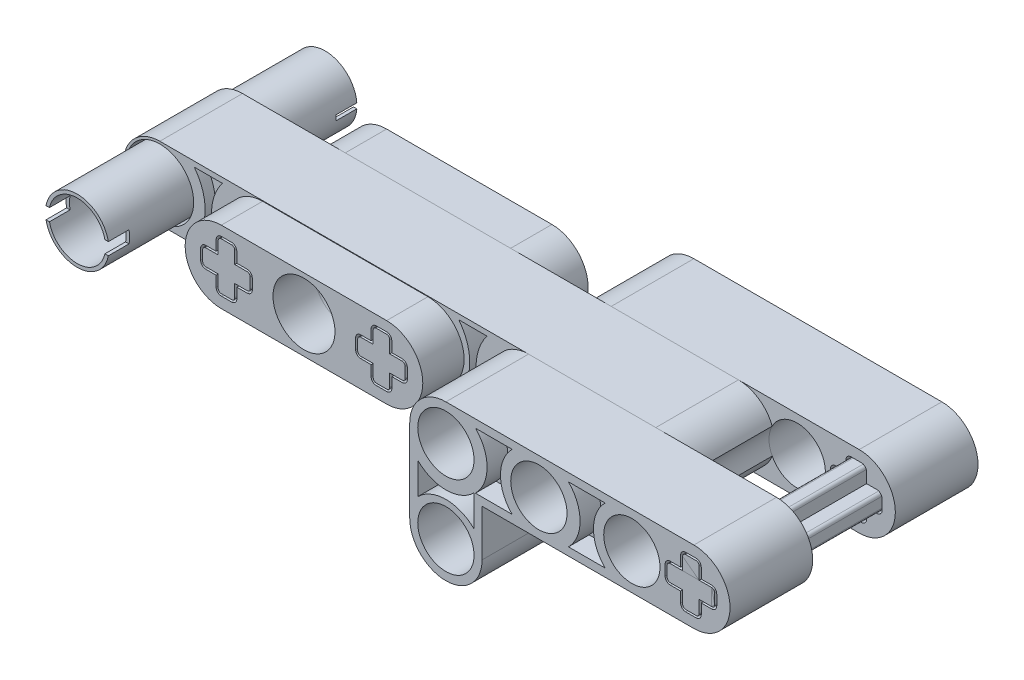
SolidWorks part; units mm, degrees
ref_plane "Front Plane" through (0, 0, 0) normal (0, 0, 1) x (1, 0, 0)
ref_plane "Top Plane" through (0, 0, 0) normal (0, 1, 0) x (1, 0, 0)
ref_plane "Right Plane" through (0, 0, 0) normal (1, 0, 0) x (0, 0, -1)
sketch "Sketch3" plane through (0, 0, 0) normal (0, 0, 1) x (1, 0, 0)
  line L0 (-24, 0) -> (24, 0) construction
  line L1 (-24, 3.5) -> (24, 3.5)
  line L2 (-24, -3.5) -> (24, -3.5)
  arc A0 (-24, 3.5) -> (-24, -3.5) centre (-24, 0) ccw
  arc A1 (24, -3.5) -> (24, 3.5) centre (24, 0) ccw
  point P3 (0, 0)
  point P8 (-27.5, 0)
  point P9 (27.5, 0)
  dimension "D1" = 7
  dimension "D2" = 55
extrude "Boss-Extrude2" add sketch "Sketch3" along normal blind 8
sketch "Sketch4" plane through (0, 0, 8) normal (0, 0, 1) x (1, 0, 0)
  line L0 (24, 3.5) -> (-24, 3.5) construction
  line L2 (-20.671, 3) -> (-17.943, 3)
  line L3 (-20.671, -3.1145) -> (-17.943, -3.1145)
  arc A1 (-20.671, 3) -> (-20.671, -3.1145) centre (-24.5637, -0.0572) cw
  arc A2 (-17.943, 3) -> (-17.943, -3.1145) centre (-14.0503, -0.0572) ccw
  point P1 (-19, -0.0572)
  point P5 (-19.614, -0.0572)
  dimension "D1" = 4.9497
  dimension "D2" = 2.728
  dimension "D3" = 19
  dimension "D4" = 0.614
  dimension "D5" = 0.5
extrude "Cut-Extrude2" cut sketch "Sketch4" against normal blind 1
sketch "Sketch5" plane through (0, 0, 8) normal (0, 0, 1) x (1, 0, 0)
  line L0 (-14.0503, -0.0572) -> (1.9497, -0.0572) construction
  line L1 (-14.0503, 3.4428) -> (1.9497, 3.4428)
  line L2 (-14.0503, -3.5572) -> (1.9497, -3.5572)
  arc A0 (-14.0503, 3.4428) -> (-14.0503, -3.5572) centre (-14.0503, -0.0572) ccw
  arc A1 (1.9497, -3.5572) -> (1.9497, 3.4428) centre (1.9497, -0.0572) ccw
  point P3 (-6.0503, -0.0572)
  dimension "D1" = 7
  dimension "D2" = 6.0503
extrude "Boss-Extrude3" add sketch "Sketch5" along normal blind 4 separate body
sketch "Sketch7" plane through (0, 0, 0) normal (0, 0, -1) x (-1, 0, 0)
  line L0 (17.943, 3) -> (20.671, 3)
  line L1 (17.943, -3.1145) -> (20.671, -3.1145)
  line L2 (-24, 3.5) -> (24, 3.5) construction
  arc A1 (17.943, 3) -> (17.943, -3.1145) centre (14.0503, -0.0572) cw
  arc A2 (20.671, 3) -> (20.671, -3.1145) centre (24.5637, -0.0572) ccw
  point P3 (19.614, -0.0572)
  point P7 (19, -0.0572)
  dimension "D1" = 4.9497
  dimension "D2" = 2.728
  dimension "D3" = 0.614
  dimension "D4" = 0.5
  dimension "D5" = 19
extrude "Cut-Extrude3" cut sketch "Sketch7" against normal blind 1
sketch "Sketch10" plane through (0, 0, 0) normal (0, 0, -1) x (-1, 0, 0)
  line L0 (-1.95, 0) -> (14.05, 0) construction
  line L1 (-1.95, 3.5) -> (14.05, 3.5)
  line L2 (-1.95, -3.5) -> (14.05, -3.5)
  line L4 (-24, 3.5) -> (24, 3.5) construction
  arc A0 (-1.95, 3.5) -> (-1.95, -3.5) centre (-1.95, 0) ccw
  arc A1 (14.05, -3.5) -> (14.05, 3.5) centre (14.05, 0) ccw
  point P2 (6.05, 0)
  point P7 (-5.45, 0)
  point P8 (17.55, 0)
  dimension "D1" = 7
  dimension "D2" = 23
  dimension "D3" = 6.05
extrude "Boss-Extrude5" add sketch "Sketch10" along normal blind 4 separate body
sketch "Sketch12" plane through (0, 0, -4) normal (0, 0, -1) x (-1, 0, 0)
  line L0 (-2.45, -1) -> (-2.45, -2)
  line L1 (-0.95, 2.5) -> (-1.95, 2.5)
  line L2 (-0.45, 2) -> (-0.45, 1)
  line L3 (-0.95, -2.5) -> (-1.95, -2.5)
  line L4 (-2.45, 2) -> (-2.45, 1)
  line L5 (-0.45, 2.5) -> (-2.45, -2.5) construction
  line L6 (-0.45, -2.5) -> (-2.45, 2.5) construction
  line L7 (0.55, 1) -> (-0.45, 1)
  line L8 (1.05, 0.5) -> (1.05, -0.5)
  line L9 (0.55, -1) -> (-0.45, -1)
  line L10 (-3.95, 0.5) -> (-3.95, -0.5)
  line L11 (1.05, 1) -> (-3.95, -1) construction
  line L12 (1.05, -1) -> (-3.95, 1) construction
  line L13 (-2.45, 1) -> (-3.45, 1)
  line L14 (-2.45, -1) -> (-3.45, -1)
  line L15 (-0.45, -1) -> (-0.45, -2)
  line L16 (-0.65, 2) -> (-0.65, 0.8)
  line L17 (0.55, 0.8) -> (-0.65, 0.8)
  line L18 (0.85, 0.5) -> (0.85, -0.5)
  line L19 (0.55, -0.8) -> (-0.65, -0.8)
  line L20 (-0.65, -0.8) -> (-0.65, -2)
  line L21 (-0.95, -2.3) -> (-1.95, -2.3)
  line L22 (-2.25, -0.8) -> (-2.25, -2)
  line L23 (-2.25, -0.8) -> (-3.45, -0.8)
  line L24 (-3.75, 0.5) -> (-3.75, -0.5)
  line L25 (-2.25, 0.8) -> (-3.45, 0.8)
  line L26 (-2.25, 2) -> (-2.25, 0.8)
  line L27 (-0.95, 2.3) -> (-1.95, 2.3)
  line L28 (12.5509, -1.0052) -> (12.5509, -2.0052)
  line L29 (14.05, 2.5) -> (13.05, 2.5)
  line L30 (14.55, 1.9943) -> (14.55, 0.9943)
  line L31 (14.051, -2.5051) -> (13.051, -2.5051)
  line L32 (12.5491, 1.9947) -> (12.5491, 0.9947)
  line L33 (15.55, 0.9943) -> (14.55, 0.9943)
  line L34 (16.05, 0.4943) -> (16.05, -0.5057)
  line L35 (15.5509, -1.0051) -> (14.5509, -1.0051)
  line L36 (11.05, 0.4943) -> (11.05, -0.5057)
  line L37 (12.5491, 0.9947) -> (11.5491, 0.9947)
  line L38 (12.5509, -1.0052) -> (11.5509, -1.0052)
  line L39 (14.5509, -1.0051) -> (14.5509, -2.0051)
  line L40 (14.35, 1.9943) -> (14.35, 0.7943)
  line L41 (15.55, 0.7943) -> (14.35, 0.7943)
  line L42 (15.85, 0.4943) -> (15.85, -0.5057)
  line L43 (15.55, -0.8057) -> (14.35, -0.8057)
  line L44 (14.35, -0.8057) -> (14.35, -2.0057)
  line L45 (14.05, -2.3057) -> (13.05, -2.3057)
  line L46 (12.75, -0.8057) -> (12.75, -2.0057)
  line L47 (12.75, -0.8057) -> (11.55, -0.8057)
  line L48 (11.25, 0.4943) -> (11.25, -0.5057)
  line L49 (12.75, 0.7943) -> (11.55, 0.7943)
  line L50 (12.75, 1.9943) -> (12.75, 0.7943)
  line L51 (14.05, 2.2943) -> (13.05, 2.2943)
  line L52 (14.55, 2.5) -> (12.55, -2.5) construction
  line L53 (14.55, -2.5) -> (12.55, 2.5) construction
  line L54 (16.05, 1) -> (11.05, -1) construction
  line L55 (16.05, -1) -> (11.05, 1) construction
  line L56 (14.05, 3.5) -> (-1.95, 3.5) construction
  arc A0 (-1.95, -2.5) -> (-2.45, -2) centre (-1.95, -2) cw
  arc A1 (-0.45, -2) -> (-0.95, -2.5) centre (-0.95, -2) cw
  arc A2 (-0.95, 2.5) -> (-0.45, 2) centre (-0.95, 2) cw
  arc A3 (-1.95, 2.5) -> (-2.45, 2) centre (-1.95, 2) ccw
  arc A4 (0.55, 1) -> (1.05, 0.5) centre (0.55, 0.5) cw
  arc A5 (1.05, -0.5) -> (0.55, -1) centre (0.55, -0.5) cw
  arc A6 (-3.45, -1) -> (-3.95, -0.5) centre (-3.45, -0.5) cw
  arc A7 (-3.45, 1) -> (-3.95, 0.5) centre (-3.45, 0.5) ccw
  arc A8 (0.55, 0.8) -> (0.85, 0.5) centre (0.55, 0.5) cw
  arc A9 (0.85, -0.5) -> (0.55, -0.8) centre (0.55, -0.5) cw
  arc A10 (-0.65, -2) -> (-0.95, -2.3) centre (-0.95, -2) cw
  arc A11 (-1.95, -2.3) -> (-2.25, -2) centre (-1.95, -2) cw
  arc A12 (-3.45, -0.8) -> (-3.75, -0.5) centre (-3.45, -0.5) cw
  arc A13 (-3.45, 0.8) -> (-3.75, 0.5) centre (-3.45, 0.5) ccw
  arc A14 (-1.95, 2.3) -> (-2.25, 2) centre (-1.95, 2) ccw
  arc A15 (-0.95, 2.3) -> (-0.65, 2) centre (-0.95, 2) cw
  arc A16 (13.051, -2.5051) -> (12.5509, -2.0052) centre (13.0509, -2.0051) cw
  arc A17 (14.5509, -2.0051) -> (14.051, -2.5051) centre (14.0509, -2.0051) cw
  arc A18 (14.05, 2.5) -> (14.55, 1.9943) centre (14.05, 2) cw
  arc A19 (13.05, 2.5) -> (12.5491, 1.9947) centre (13.0491, 2) ccw
  arc A20 (15.55, 0.9943) -> (16.05, 0.4943) centre (15.55, 0.4943) cw
  arc A21 (16.05, -0.5057) -> (15.5509, -1.0051) centre (15.55, -0.5051) cw
  arc A22 (11.5509, -1.0052) -> (11.05, -0.5057) centre (11.55, -0.5053) cw
  arc A23 (11.5491, 0.9947) -> (11.05, 0.4943) centre (11.55, 0.4948) ccw
  arc A24 (15.55, 0.7943) -> (15.85, 0.4943) centre (15.55, 0.4943) cw
  arc A25 (15.85, -0.5057) -> (15.55, -0.8057) centre (15.55, -0.5057) cw
  arc A26 (14.35, -2.0057) -> (14.05, -2.3057) centre (14.05, -2.0057) cw
  arc A27 (13.05, -2.3057) -> (12.75, -2.0057) centre (13.05, -2.0057) cw
  arc A28 (11.55, -0.8057) -> (11.25, -0.5057) centre (11.55, -0.5057) cw
  arc A29 (11.55, 0.7943) -> (11.25, 0.4943) centre (11.55, 0.4943) ccw
  arc A30 (13.05, 2.2943) -> (12.75, 1.9943) centre (13.05, 1.9943) ccw
  arc A31 (14.05, 2.2943) -> (14.35, 1.9943) centre (14.05, 1.9943) cw
  arc A33 (14.05, -3.5) -> (14.05, 3.5) centre (14.05, 0) ccw construction
  point P0 (0, 0)
  point P6 (0, 0)
  point P69 (13.55, 0)
  point P74 (13.55, 0)
  point P135 (11.05, -0.0057)
  point P140 (17.55, 0)
  point P141 (-1.45, 0)
  dimension "D5" = 0.5
  dimension "D3" = 0.5
  dimension "D2" = 1
  dimension "D4" = 5
  dimension "D6" = 1
  dimension "D9" = 6.5
  dimension "D10" = 4
  dimension "D8" = 1
  dimension "D11" = 5
  dimension "D12" = 0.2
  dimension "D13" = 0.2
  dimension "D14" = 15
  dimension "D15" = 1
  dimension "D16" = 0.2009
  dimension "D17" = 0.2
  dimension "D18" = 0.2009
  dimension "D19" = 0.1994
  dimension "D20" = 0.1991
  dimension "D7" = 0.2
extrude "Cut-Extrude6" cut sketch "Sketch12" against normal through all
sketch "Sketch13" plane through (0, 0, 8) normal (0, 0, 1) x (1, 0, 0)
  circle A0 centre (-24, 0) radius 3.275
  circle A1 centre (-24, 0) radius 3.075
  dimension "D1" = 6.55
  dimension "D2" = 6.15
extrude "Cut-Extrude8" cut sketch "Sketch13" against normal through all
sketch "Sketch17" plane through (0, 0, -4) normal (0, 0, -1) x (-1, 0, 0)
  line L0 (-2.4539, -1) -> (-2.4539, -2)
  line L1 (-0.9539, 2.5) -> (-1.9539, 2.5)
  line L2 (-0.4539, 2) -> (-0.4539, 1)
  line L3 (-0.9539, -2.5) -> (-1.9539, -2.5)
  line L4 (-2.4539, 2) -> (-2.4539, 1)
  line L5 (-0.4539, 2.5) -> (-2.4539, -2.5) construction
  line L6 (-0.4539, -2.5) -> (-2.4539, 2.5) construction
  line L7 (0.5461, 1) -> (-0.4539, 1)
  line L8 (1.0461, 0.5) -> (1.0461, -0.5)
  line L9 (0.5461, -1) -> (-0.4539, -1)
  line L10 (-3.9539, 0.5) -> (-3.9539, -0.5)
  line L11 (1.0461, 1) -> (-3.9539, -1) construction
  line L12 (1.0461, -1) -> (-3.9539, 1) construction
  line L13 (-2.4539, 1) -> (-3.4539, 1)
  line L14 (-2.4539, -1) -> (-3.4539, -1)
  line L15 (-0.4539, -1) -> (-0.4539, -2)
  line L16 (-0.6539, 2) -> (-0.6539, 0.8)
  line L17 (0.5461, 0.8) -> (-0.6539, 0.8)
  line L18 (0.8461, 0.5) -> (0.8461, -0.5)
  line L19 (0.5461, -0.8) -> (-0.6539, -0.8)
  line L20 (-0.6539, -0.8) -> (-0.6539, -2)
  line L21 (-0.9539, -2.3) -> (-1.9539, -2.3)
  line L22 (-2.2539, -0.8) -> (-2.2539, -2)
  line L23 (-2.2539, -0.8) -> (-3.4539, -0.8)
  line L24 (-3.7539, 0.5) -> (-3.7539, -0.5)
  line L25 (-2.2539, 0.8) -> (-3.4539, 0.8)
  line L26 (-2.2539, 2) -> (-2.2539, 0.8)
  line L27 (-0.9539, 2.3) -> (-1.9539, 2.3)
  line L52 (12.55, -1) -> (12.55, -2)
  line L53 (14.05, 2.5) -> (13.05, 2.5)
  line L54 (14.55, 2) -> (14.55, 1)
  line L55 (14.05, -2.5) -> (13.05, -2.5)
  line L56 (14.05, 3.5) -> (-1.95, 3.5) construction
  line L57 (12.55, 2) -> (12.55, 1)
  line L58 (15.55, 1) -> (14.55, 1)
  line L59 (16.05, 0.5) -> (16.05, -0.5)
  line L60 (15.55, -1) -> (14.55, -1)
  line L61 (11.05, 0.5) -> (11.05, -0.5)
  line L62 (12.55, 1) -> (11.55, 1)
  line L63 (12.55, -1) -> (11.55, -1)
  line L64 (14.55, -1) -> (14.55, -2)
  line L65 (14.35, 2) -> (14.35, 0.8)
  line L66 (15.55, 0.8) -> (14.35, 0.8)
  line L67 (15.85, 0.5) -> (15.85, -0.5)
  line L68 (15.55, -0.8) -> (14.35, -0.8)
  line L69 (14.35, -0.8) -> (14.35, -2)
  line L70 (14.05, -2.3) -> (13.05, -2.3)
  line L71 (12.75, -0.8) -> (12.75, -2)
  line L72 (12.75, -0.8) -> (11.55, -0.8)
  line L73 (11.25, 0.5) -> (11.25, -0.5)
  line L74 (12.75, 0.8) -> (11.55, 0.8)
  line L75 (12.75, 2) -> (12.75, 0.8)
  line L76 (14.05, 2.3) -> (13.05, 2.3)
  line L77 (14.55, 2.5) -> (12.55, -2.5) construction
  line L78 (14.55, -2.5) -> (12.55, 2.5) construction
  line L79 (16.05, 1) -> (11.05, -1) construction
  line L80 (16.05, -1) -> (11.05, 1) construction
  arc A0 (-1.9539, -2.5) -> (-2.4539, -2) centre (-1.9539, -2) cw
  arc A1 (-0.4539, -2) -> (-0.9539, -2.5) centre (-0.9539, -2) cw
  arc A2 (-0.9539, 2.5) -> (-0.4539, 2) centre (-0.9539, 2) cw
  arc A3 (-1.9539, 2.5) -> (-2.4539, 2) centre (-1.9539, 2) ccw
  arc A4 (0.5461, 1) -> (1.0461, 0.5) centre (0.5461, 0.5) cw
  arc A5 (1.0461, -0.5) -> (0.5461, -1) centre (0.5461, -0.5) cw
  arc A6 (-3.4539, -1) -> (-3.9539, -0.5) centre (-3.4539, -0.5) cw
  arc A7 (-3.4539, 1) -> (-3.9539, 0.5) centre (-3.4539, 0.5) ccw
  arc A8 (0.5461, 0.8) -> (0.8461, 0.5) centre (0.5461, 0.5) cw
  arc A9 (0.8461, -0.5) -> (0.5461, -0.8) centre (0.5461, -0.5) cw
  arc A10 (-0.6539, -2) -> (-0.9539, -2.3) centre (-0.9539, -2) cw
  arc A11 (-1.9539, -2.3) -> (-2.2539, -2) centre (-1.9539, -2) cw
  arc A12 (-3.4539, -0.8) -> (-3.7539, -0.5) centre (-3.4539, -0.5) cw
  arc A13 (-3.4539, 0.8) -> (-3.7539, 0.5) centre (-3.4539, 0.5) ccw
  arc A14 (-1.9539, 2.3) -> (-2.2539, 2) centre (-1.9539, 2) ccw
  arc A15 (-0.9539, 2.3) -> (-0.6539, 2) centre (-0.9539, 2) cw
  arc A32 (13.05, -2.5) -> (12.55, -2) centre (13.05, -2) cw
  arc A33 (14.55, -2) -> (14.05, -2.5) centre (14.05, -2) cw
  arc A34 (14.05, 2.5) -> (14.55, 2) centre (14.05, 2) cw
  arc A35 (13.05, 2.5) -> (12.55, 2) centre (13.05, 2) ccw
  arc A36 (15.55, 1) -> (16.05, 0.5) centre (15.55, 0.5) cw
  arc A37 (16.05, -0.5) -> (15.55, -1) centre (15.55, -0.5) cw
  arc A38 (11.55, -1) -> (11.05, -0.5) centre (11.55, -0.5) cw
  arc A39 (11.55, 1) -> (11.05, 0.5) centre (11.55, 0.5) ccw
  arc A40 (15.55, 0.8) -> (15.85, 0.5) centre (15.55, 0.5) cw
  arc A41 (15.85, -0.5) -> (15.55, -0.8) centre (15.55, -0.5) cw
  arc A42 (14.35, -2) -> (14.05, -2.3) centre (14.05, -2) cw
  arc A43 (13.05, -2.3) -> (12.75, -2) centre (13.05, -2) cw
  arc A44 (11.55, -0.8) -> (11.25, -0.5) centre (11.55, -0.5) cw
  arc A45 (11.55, 0.8) -> (11.25, 0.5) centre (11.55, 0.5) ccw
  arc A46 (13.05, 2.3) -> (12.75, 2) centre (13.05, 2) ccw
  arc A47 (14.05, 2.3) -> (14.35, 2) centre (14.05, 2) cw
  arc A48 (14.05, -3.5) -> (14.05, 3.5) centre (14.05, 0) ccw construction
  arc A49 (-1.95, 3.5) -> (-1.95, -3.5) centre (-1.95, 0) ccw construction
  point P0 (-0.0039, 0.2841)
  point P5 (-0.0039, 0.2841)
  point P67 (15, 0.2841)
  point P72 (15, 0.2841)
  point P137 (17.55, 0)
  point P141 (-5.45, 0)
  dimension "D3" = 0.5
  dimension "D4" = 2
  dimension "D1" = 5
  dimension "D2" = 1
  dimension "D5" = 6.5
  dimension "D6" = 6.4961
  dimension "D15" = 1
  dimension "D16" = 1.2
extrude "Cut-Extrude9" cut sketch "Sketch17" against normal through all
sketch "Sketch20" plane through (0, 0, -4) normal (0, 0, -1) x (-1, 0, 0)
  line L0 (14.05, 3.5) -> (-1.95, 3.5) construction
  circle A0 centre (6.05, 0) radius 3
  arc A1 (-1.95, 3.5) -> (-1.95, -3.5) centre (-1.95, 0) ccw construction
  dimension "D1" = 6
  dimension "D2" = 3.5
  dimension "D3" = 8
extrude "Cut-Extrude10" cut sketch "Sketch20" against normal through all
sketch "Sketch21" plane through (0, 0, 8) normal (0, 0, 1) x (1, 0, 0)
  circle A0 centre (-24, 0) radius 3.075
  circle A1 centre (-24, 0) radius 2.75
extrude "Boss-Extrude6" add sketch "Sketch21" along normal blind 8 and the other way blind 16
sketch "Sketch22" plane through (0, 0, 16) normal (0, 0, 1) x (1, 0, 0)
  line L1 (-20.779, 0.5924) -> (-27.221, 0.5924)
  line L2 (-20.779, 0.5924) -> (-20.779, -0.5924)
  line L3 (-20.779, -0.5924) -> (-27.221, -0.5924)
  line L4 (-27.221, 0.5924) -> (-27.221, -0.5924)
  line L5 (-20.779, 0.5924) -> (-27.221, -0.5924) construction
  line L6 (-20.779, -0.5924) -> (-27.221, 0.5924) construction
  circle A0 centre (-24, 0) radius 3.275 construction
  point P0 (-24, 0)
  dimension "D1" = 1.1848
extrude "Cut-Extrude11" cut sketch "Sketch22" against normal blind 2
sketch "Sketch23" plane through (0, 0, -8) normal (0, 0, -1) x (-1, 0, 0)
  line L1 (27.2654, 0.25) -> (20.7346, 0.25)
  line L2 (27.2654, 0.25) -> (27.2654, -0.25)
  line L3 (27.2654, -0.25) -> (20.7346, -0.25)
  line L4 (20.7346, 0.25) -> (20.7346, -0.25)
  line L5 (27.2654, 0.25) -> (20.7346, -0.25) construction
  line L6 (27.2654, -0.25) -> (20.7346, 0.25) construction
  circle A0 centre (24, 0) radius 3.275 construction
  point P0 (24, 0)
  dimension "D1" = 0.5
extrude "Cut-Extrude12" cut sketch "Sketch23" against normal blind 2
sketch "Sketch24" plane through (0, 0, 8) normal (0, 0, 1) x (1, 0, 0)
  circle A0 centre (-24, 0) radius 2.75
extrude "Cut-Extrude13" cut sketch "Sketch24" against normal through all
sketch "Sketch26" plane through (0, 0, 8) normal (0, 0, 1) x (1, 0, 0)
  line L0 (4.943, 3) -> (7.671, 3)
  line L1 (4.943, -3.1145) -> (7.671, -3.1145)
  line L2 (24, 3.5) -> (-24, 3.5) construction
  arc A0 (4.943, 3) -> (4.943, -3.1145) centre (1.0503, -0.0572) cw
  arc A1 (7.671, 3) -> (7.671, -3.1145) centre (11.5637, -0.0572) ccw
  point P0 (6.614, -0.0572)
  point P4 (6, -0.0572)
  dimension "D1" = 4.9497
  dimension "D5" = 6
  dimension "D2" = 2.728
  dimension "D3" = 0.614
  dimension "D4" = 0.5
extrude "Cut-Extrude14" cut sketch "Sketch26" against normal blind 2
ref_plane "Plane1" through (0, 0, 8) normal (0, 0, 1) x (1, 0, 0)
sketch "Sketch29" plane through (0, 0, 8) normal (0, 0, 1) x (1, 0, 0)
  line L0 (8.187, 0) -> (8.187, -8)
  line L1 (11.687, 3.5) -> (35.687, 3.5)
  line L2 (35.687, -3.5) -> (15.187, -3.5)
  line L3 (15.187, -3.5) -> (15.187, -8)
  line L4 (24, 3.5) -> (-24, 3.5) construction
  arc A0 (8.187, -8) -> (15.187, -8) centre (11.687, -8) ccw
  arc A1 (8.187, 0) -> (11.687, 3.5) centre (11.687, 0) cw
  arc A2 (15.187, -8) -> (8.187, -8) centre (11.687, -8) cw
  arc A3 (35.687, 3.5) -> (35.687, -3.5) centre (35.687, 0) cw
  point P0 (39.187, 0)
  point P10 (11.687, -11.5)
  dimension "D5" = 3.5
  dimension "D6" = 3.5
  dimension "D7" = 3.5
  dimension "D10" = 11.687
  dimension "D1" = 31
  dimension "D2" = 15
  dimension "D3" = 7
  dimension "D4" = 7
  dimension "D8" = 8.187
  dimension "D9" = 11.687
extrude "Boss-Extrude8" add sketch "Sketch29" along normal blind 8 separate body contours A3 L1 A1 L0 A0 L3 L2 region at (21.1948, -1.4269, 8)
sketch "Sketch36" plane through (0, 0, 0) normal (0, 0, -1) x (-1, 0, 0)
  line L0 (-35.687, -3.5) -> (-15.187, -3.5) construction
  line L1 (-24, 3.5) -> (24, 3.5) construction
  line L2 (-8.187, 0) -> (-8.187, -8) construction
  line L3 (-35.687, 3.5) -> (-11.687, 3.5)
  line L4 (-8.187, 0) -> (-8.187, -8)
  line L5 (-15.187, -8) -> (-15.187, -3.5)
  line L6 (-15.187, -3.5) -> (-35.687, -3.5)
  arc A1 (-15.187, -8) -> (-8.187, -8) centre (-11.687, -8) ccw
  arc A3 (-15.187, -8) -> (-8.187, -8) centre (-11.687, -8) ccw construction
  arc A4 (-35.687, 3.5) -> (-35.687, -3.5) centre (-35.687, 0) ccw
  arc A5 (-35.687, 3.5) -> (-35.687, -3.5) centre (-35.687, 0) ccw construction
  arc A6 (-11.687, 3.5) -> (-8.187, 0) centre (-11.687, 0) cw
extrude "Boss-Extrude10" add sketch "Sketch36" along normal blind 8 separate body
sketch "Sketch40" plane through (0, 0, -8) normal (0, 0, -1) x (-1, 0, 0)
  line L0 (-36.4025, -1) -> (-36.4025, -2)
  line L1 (-34.9025, 2.5) -> (-35.9025, 2.5)
  line L2 (-34.4025, 2) -> (-34.4025, 1)
  line L3 (-34.9025, -2.5) -> (-35.9025, -2.5)
  line L4 (-36.4025, 2) -> (-36.4025, 1)
  line L5 (-34.4025, 2.5) -> (-36.4025, -2.5) construction
  line L6 (-34.4025, -2.5) -> (-36.4025, 2.5) construction
  line L7 (-33.4025, 1) -> (-34.4025, 1)
  line L8 (-32.9025, 0.5) -> (-32.9025, -0.5)
  line L9 (-33.4025, -1) -> (-34.4025, -1)
  line L10 (-37.9025, 0.5) -> (-37.9025, -0.5)
  line L11 (-32.9025, 1) -> (-37.9025, -1) construction
  line L12 (-32.9025, -1) -> (-37.9025, 1) construction
  line L13 (-36.4025, 1) -> (-37.4025, 1)
  line L14 (-36.4025, -1) -> (-37.4025, -1)
  line L15 (-34.4025, -1) -> (-34.4025, -2)
  line L16 (-34.6025, 2) -> (-34.6025, 0.8)
  line L17 (-33.4025, 0.8) -> (-34.6025, 0.8)
  line L18 (-33.1025, 0.5) -> (-33.1025, -0.5)
  line L19 (-33.4025, -0.8) -> (-34.6025, -0.8)
  line L20 (-34.6025, -0.8) -> (-34.6025, -2)
  line L21 (-34.9025, -2.3) -> (-35.9025, -2.3)
  line L22 (-36.2025, -0.8) -> (-36.2025, -2)
  line L23 (-36.2025, -0.8) -> (-37.4025, -0.8)
  line L24 (-37.7025, 0.5) -> (-37.7025, -0.5)
  line L25 (-36.2025, 0.8) -> (-37.4025, 0.8)
  line L26 (-36.2025, 2) -> (-36.2025, 0.8)
  line L27 (-34.9025, 2.3) -> (-35.9025, 2.3)
  line L28 (-11.687, 3.5) -> (-35.687, 3.5) construction
  arc A0 (-35.9025, -2.5) -> (-36.4025, -2) centre (-35.9025, -2) cw
  arc A1 (-34.4025, -2) -> (-34.9025, -2.5) centre (-34.9025, -2) cw
  arc A2 (-34.9025, 2.5) -> (-34.4025, 2) centre (-34.9025, 2) cw
  arc A3 (-35.9025, 2.5) -> (-36.4025, 2) centre (-35.9025, 2) ccw
  arc A4 (-33.4025, 1) -> (-32.9025, 0.5) centre (-33.4025, 0.5) cw
  arc A5 (-32.9025, -0.5) -> (-33.4025, -1) centre (-33.4025, -0.5) cw
  arc A6 (-37.4025, -1) -> (-37.9025, -0.5) centre (-37.4025, -0.5) cw
  arc A7 (-37.4025, 1) -> (-37.9025, 0.5) centre (-37.4025, 0.5) ccw
  arc A8 (-33.4025, 0.8) -> (-33.1025, 0.5) centre (-33.4025, 0.5) cw
  arc A9 (-33.1025, -0.5) -> (-33.4025, -0.8) centre (-33.4025, -0.5) cw
  arc A10 (-34.6025, -2) -> (-34.9025, -2.3) centre (-34.9025, -2) cw
  arc A11 (-35.9025, -2.3) -> (-36.2025, -2) centre (-35.9025, -2) cw
  arc A12 (-37.4025, -0.8) -> (-37.7025, -0.5) centre (-37.4025, -0.5) cw
  arc A13 (-37.4025, 0.8) -> (-37.7025, 0.5) centre (-37.4025, 0.5) ccw
  arc A14 (-35.9025, 2.3) -> (-36.2025, 2) centre (-35.9025, 2) ccw
  arc A15 (-34.9025, 2.3) -> (-34.6025, 2) centre (-34.9025, 2) cw
  arc A16 (-35.687, 3.5) -> (-35.687, -3.5) centre (-35.687, 0) ccw construction
  point P0 (-33.9525, 0.3228)
  point P5 (-33.9525, 0.3228)
  point P68 (-35.4025, 2.3)
  point P72 (-39.187, 0)
  dimension "D3" = 0.5
  dimension "D1" = 5
  dimension "D2" = 1
  dimension "D4" = 1
  dimension "D5" = 0.2
  dimension "D6" = 0.2
  dimension "D7" = 1.2845
extrude "Cut-Extrude19" cut sketch "Sketch40" against normal through all
sketch "Sketch41" plane through (0, 0, -8) normal (0, 0, -1) x (-1, 0, 0)
  line L40 (-34.6025, 2) -> (-34.6025, 0.8)
  line L41 (-33.4025, 0.8) -> (-34.6025, 0.8)
  line L42 (-33.1025, 0.5) -> (-33.1025, -0.5)
  line L43 (-33.4025, -0.8) -> (-34.6025, -0.8)
  line L44 (-34.6025, -0.8) -> (-34.6025, -2)
  line L45 (-34.9025, -2.3) -> (-35.9025, -2.3)
  line L46 (-36.2025, -0.8) -> (-36.2025, -2)
  line L47 (-36.2025, -0.8) -> (-37.4025, -0.8)
  line L48 (-37.7025, 0.5) -> (-37.7025, -0.5)
  line L49 (-36.2025, 0.8) -> (-37.4025, 0.8)
  line L50 (-36.2025, 2) -> (-36.2025, 0.8)
  line L51 (-34.9025, 2.3) -> (-35.9025, 2.3)
  arc A24 (-33.4025, 0.8) -> (-33.1025, 0.5) centre (-33.4025, 0.5) cw
  arc A25 (-33.1025, -0.5) -> (-33.4025, -0.8) centre (-33.4025, -0.5) cw
  arc A26 (-34.6025, -2) -> (-34.9025, -2.3) centre (-34.9025, -2) cw
  arc A27 (-35.9025, -2.3) -> (-36.2025, -2) centre (-35.9025, -2) cw
  arc A28 (-37.4025, -0.8) -> (-37.7025, -0.5) centre (-37.4025, -0.5) cw
  arc A29 (-37.4025, 0.8) -> (-37.7025, 0.5) centre (-37.4025, 0.5) ccw
  arc A30 (-35.9025, 2.3) -> (-36.2025, 2) centre (-35.9025, 2) ccw
  arc A31 (-34.9025, 2.3) -> (-34.6025, 2) centre (-34.9025, 2) cw
  point P0 (-33.8342, 0.1396)
  point P5 (-33.8342, 0.1396)
extrude "Boss-Extrude11" add sketch "Sketch41" against normal blind 24 separate body
sketch "Sketch42" plane through (0, 0, -8) normal (0, 0, -1) x (-1, 0, 0)
  circle A0 centre (-11.687, 0) radius 2.7252
  circle A1 centre (-20.687, 0) radius 2.7252
  circle A2 centre (-29.687, 0) radius 2.7252
  circle A3 centre (-20.687, -8) radius 2.7252 [skipped]
  circle A4 centre (-29.687, -8) radius 2.7252 [skipped]
  circle A5 centre (-11.687, -8) radius 2.7252
  dimension "D3" = 5.4504
  dimension "D4" = 9
  dimension "D5" = 8
  dimension "D6" = 3.5
  dimension "D1" = 3
  dimension "D2" = 2
extrude "Cut-Extrude20" cut sketch "Sketch42" against normal through all
sketch "Sketch43" plane through (0, 0, -8) normal (0, 0, -1) x (-1, 0, 0)
  line L0 (-26.9618, 2.7252) -> (-23.4122, 2.7252)
  line L2 (-23.4122, -2.7252) -> (-26.9618, -2.7252)
  line L4 (-11.687, 3.5) -> (-35.687, 3.5) construction
  line L5 (-17.9618, 2.7252) -> (-14.4122, 2.7252)
  line L6 (-14.4122, -2.7252) -> (-17.9618, -2.7252)
  arc A0 (-26.9618, 2.7252) -> (-26.9618, -2.7252) centre (-29.687, 0) cw
  arc A1 (-23.4122, 2.7252) -> (-23.4122, -2.7252) centre (-20.687, 0) ccw
  arc A2 (-34.9025, -2.3) -> (-34.6025, -2) centre (-34.9025, -2) ccw construction
  arc A3 (-14.4122, 2.7252) -> (-14.4122, -2.7252) centre (-11.687, 0) ccw
  arc A4 (-17.9618, 2.7252) -> (-17.9618, -2.7252) centre (-20.687, 0) cw
  dimension "D3" = 3.854
  dimension "D4" = 7.9407
  dimension "D1" = 3.5496
  dimension "D2" = 0.7748
  dimension "D5" = 4.9155
  dimension "D7" = 5.4504
  dimension "D6" = 2
extrude "Cut-Extrude21" cut sketch "Sketch43" against normal blind 2
sketch "Sketch44" plane through (0, 0, 16) normal (0, 0, 1) x (1, 0, 0)
  line L0 (14.5469, 2.7252) -> (18.0965, 2.7252)
  line L1 (18.0965, -2.7252) -> (14.5469, -2.7252)
  line L2 (23.5469, 2.7252) -> (27.0965, 2.7252)
  line L3 (27.0965, -2.7252) -> (23.5469, -2.7252)
  line L4 (35.687, -3.5) -> (15.187, -3.5) construction
  line L5 (11.687, 3.5) -> (35.687, 3.5) construction
  arc A0 (14.5469, 2.7252) -> (14.5469, -2.7252) centre (11.8217, 0) cw
  arc A1 (18.0965, 2.7252) -> (18.0965, -2.7252) centre (20.8217, 0) ccw
  arc A2 (27.0965, 2.7252) -> (27.0965, -2.7252) centre (29.8217, 0) ccw
  arc A3 (23.5469, 2.7252) -> (23.5469, -2.7252) centre (20.8217, 0) cw
  circle A4 centre (11.687, 0) radius 2.7252 construction
  point P12 (11.687, 2.7252)
  dimension "D2" = 3.854
  dimension "D8" = 3.854
  dimension "D1" = 3.5496
  dimension "D3" = 5.4504
  dimension "D4" = 12.5969
  dimension "D5" = 0.7748
  dimension "D6" = 5.4504
  dimension "D7" = 5.4504
  dimension "D9" = 0.7748
  dimension "D10" = 3.5496
extrude "Cut-Extrude22" cut sketch "Sketch44" against normal blind 2
sketch "Sketch45" plane through (0, 0, 16) normal (0, 0, 1) x (1, 0, 0)
  line L0 (8.971, -2.7586) -> (8.971, -5.8018)
  line L2 (14.418, -5.8018) -> (14.418, -2.7586)
  line L4 (8.187, 0) -> (8.187, -8) construction
  arc A0 (8.971, -2.7586) -> (14.418, -2.7586) centre (11.6945, -0.0317) ccw
  arc A1 (8.971, -5.8018) -> (14.418, -5.8018) centre (11.6945, -8.5287) cw
  dimension "D2" = 3.854
  dimension "D1" = 0.784
  dimension "D3" = 2.1982
  dimension "D4" = 5.447
  dimension "D5" = 3.0433
extrude "Cut-Extrude23" cut sketch "Sketch45" against normal blind 2
sketch "Sketch46" plane through (0, 0, -8) normal (0, 0, -1) x (-1, 0, 0)
  line L0 (-14.4122, -2.8151) -> (-14.4122, -5.8583)
  line L1 (-8.9652, -5.8583) -> (-8.9652, -2.8151)
  line L2 (-15.187, -3.5) -> (-15.187, -8) construction
  arc A0 (-14.4122, -2.8151) -> (-8.9652, -2.8151) centre (-11.6887, -0.0882) ccw
  arc A1 (-14.4122, -5.8583) -> (-8.9652, -5.8583) centre (-11.6887, -8.5852) cw
  circle A2 centre (-11.687, -8) radius 2.7252 construction
  point P7 (-14.4122, -8)
  dimension "D1" = 3.854
  dimension "D2" = 5.447
  dimension "D3" = 3.0433
  dimension "D4" = 0.7748
  dimension "D5" = 3.4634
extrude "Cut-Extrude24" cut sketch "Sketch46" against normal blind 2
sketch "Sketch48" plane through (0, 0, 0) normal (0, 0, -1) x (-1, 0, 0)
  line L0 (-7.9381, 3.001) -> (-5.2101, 3.001)
  line L1 (-7.9381, -3.1134) -> (-5.2101, -3.1134)
  line L2 (24, -3.5) -> (-24, -3.5) construction
  arc A0 (-7.9381, 3.001) -> (-7.9381, -3.1134) centre (-11.8309, -0.0562) cw
  arc A1 (-5.2101, 3.001) -> (-5.2101, -3.1134) centre (-1.3174, -0.0562) ccw
  point P0 (-6.2671, -0.0562)
  point P4 (-6.8811, -0.0562)
  dimension "D1" = 4.9497
  dimension "D2" = 2.728
  dimension "D3" = 0.614
  dimension "D4" = 0.3866
  dimension "D5" = 5.2101
extrude "Cut-Extrude25" cut sketch "Sketch48" against normal blind 2
ref_plane "Plane2" through (0, 0, -8) normal (0, 0, -1) x (-1, 0, 0)
sketch "Sketch49" plane through (0, 0, -8) normal (0, 0, -1) x (-1, 0, 0)
  line L0 (-28.2478, -3.5) -> (-16.833, -3.5) construction
  line L4 (-11.687, 3.5) -> (-35.687, 3.5) construction
  line L5 (-16.8799, 3.5) -> (-16.8799, -2.7252)
  line L6 (-35.687, -3.5) -> (-15.187, -3.5) construction
  line L7 (-27.9542, 3.5) -> (-16.8799, 3.5)
  spline S0 degree 2 poles (-27.9542, 3.5) (-20.0835, 2.8323) (-16.8799, -2.7252) knots 0.04255 0.04255 0.04255 1 1 1
